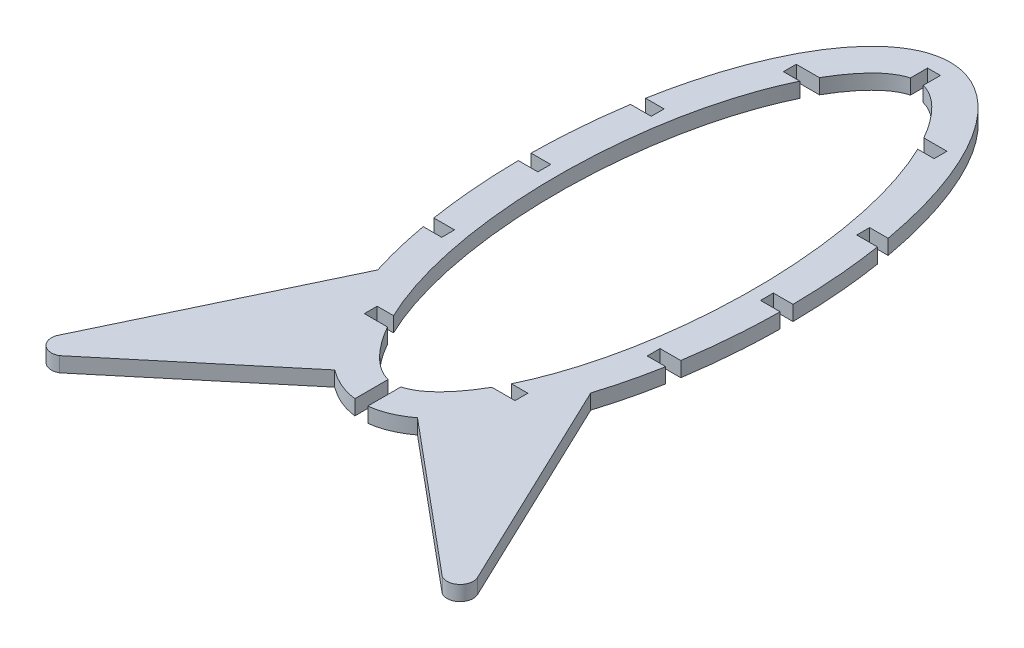
SolidWorks part; units mm, degrees
ref_plane "Front Plane" through (0, 0, 0) normal (0, 0, 1) x (1, 0, 0)
ref_plane "Top Plane" through (0, 0, 0) normal (0, 1, 0) x (1, 0, 0)
ref_plane "Right Plane" through (0, 0, 0) normal (1, 0, 0) x (0, 0, -1)
sketch "Sketch1" plane through (0, 0, 0) normal (0, 1, 0) x (1, 0, 0)
  line L2 (25.4, 0) -> (-45.1447, 0) construction
  line L3 (21.59, 0) -> (30.3971, 0) construction
  line L4 (21.59, 1.2446) -> (25.394, 1.2446)
  line L5 (21.59, 1.2446) -> (21.59, -1.2446)
  line L6 (21.59, -1.2446) -> (25.394, -1.2446)
  line L8 (37.0979, -78.485) -> (8.0291, -54.2196)
  line L9 (40.6569, -75.1899) -> (20.6588, -33.2492)
  line L10 (23.7402, 20.32) -> (29.3413, 20.32) construction
  line L11 (19.9302, 21.5646) -> (23.5224, 21.5646)
  line L12 (19.9302, 21.5646) -> (19.9302, 19.0754)
  line L13 (19.9302, 19.0754) -> (23.9434, 19.0754)
  line L19 (14.0482, 40.64) -> (-23.5224, 40.64) construction
  line L20 (0, 57.15) -> (0, 53.975) construction
  line L21 (-37.0979, -78.485) -> (-8.0291, -54.2196)
  line L22 (-14.6132, -41.8846) -> (-10.1242, -41.8846)
  line L23 (-14.6132, -41.8846) -> (-14.6132, -39.3954)
  line L24 (-14.6132, -39.3954) -> (-11.4313, -39.3954)
  line L25 (19.9302, -21.5646) -> (23.5224, -21.5646)
  line L26 (19.9302, -21.5646) -> (19.9302, -19.0754)
  line L27 (19.9302, -19.0754) -> (23.9434, -19.0754)
  line L28 (-40.6569, -75.1899) -> (-20.6588, -33.2492)
  line L29 (14.6132, 41.8846) -> (10.1242, 41.8846)
  line L30 (14.6132, 41.8846) -> (14.6132, 39.3954)
  line L31 (14.6132, 39.3954) -> (11.4313, 39.3954)
  line L32 (-19.9302, -21.5646) -> (-23.5224, -21.5646)
  line L33 (-19.9302, -21.5646) -> (-19.9302, -19.0754)
  line L34 (-19.9302, -19.0754) -> (-23.9434, -19.0754)
  line L35 (-21.59, 1.2446) -> (-21.59, -1.2446)
  line L36 (-21.59, 1.2446) -> (-25.394, 1.2446)
  line L37 (-21.59, -1.2446) -> (-25.394, -1.2446)
  line L38 (-19.9302, 21.5646) -> (-23.5224, 21.5646)
  line L39 (-19.9302, 21.5646) -> (-19.9302, 19.0754)
  line L40 (-19.9302, 19.0754) -> (-23.9434, 19.0754)
  line L41 (14.6132, -39.3954) -> (11.4313, -39.3954)
  line L42 (-14.6132, 41.8846) -> (-10.1242, 41.8846)
  line L43 (-14.6132, 41.8846) -> (-14.6132, 39.3954)
  line L44 (-14.6132, 39.3954) -> (-11.4313, 39.3954)
  line L46 (0, 39.3954) -> (0, -57.15) construction
  line L47 (14.6132, -41.8846) -> (14.6132, -39.3954)
  line L48 (14.6132, -41.8846) -> (10.1242, -41.8846)
  line L49 (1.2446, -53.975) -> (1.2446, -50.6449)
  line L50 (-1.2446, 53.975) -> (1.2446, 53.975)
  line L51 (-1.2446, 53.975) -> (-1.2446, 50.6449)
  line L53 (1.2446, 53.975) -> (1.2446, 50.6449)
  line L54 (1.2446, -53.975) -> (1.2446, -57.0814)
  line L55 (-1.2446, -53.975) -> (-1.2446, -50.6449)
  line L56 (-1.2446, -53.975) -> (-1.2446, -57.0814)
  arc A0 (37.0979, -78.485) -> (40.6569, -75.1899) centre (38.3642, -76.2831) ccw
  arc A1 (-37.0979, -78.485) -> (-40.6569, -75.1899) centre (-38.3642, -76.2831) cw
  ellipse E0 centre (0, 0) end of major axis (0, 57.15) minor radius 25.4 (-23.9434, 19.0754) -> (-25.394, 1.2446) ccw
  ellipse E1 centre (0, 0) end of major axis (0, 57.15) minor radius 25.4 (-25.394, -1.2446) -> (-23.9434, -19.0754) ccw
  ellipse E2 centre (0, 0) end of major axis (0, 57.15) minor radius 25.4 (-23.5224, -21.5646) -> (-20.6588, -33.2492) ccw
  ellipse E3 centre (0, 0) end of major axis (0, 57.15) minor radius 25.4 (23.9434, -19.0754) -> (25.394, -1.2446) ccw
  ellipse E4 centre (0, 0) end of major axis (0, 57.15) minor radius 25.4 (25.394, 1.2446) -> (23.9434, 19.0754) ccw
  ellipse E5 centre (0, 0) end of major axis (0, 57.15) minor radius 25.4 (23.5224, 21.5646) -> (-23.5224, 21.5646) ccw
  ellipse E6 centre (0, 0) end of major axis (0, 57.15) minor radius 25.4 (1.2446, -57.0814) -> (8.0291, -54.2196) ccw
  ellipse E7 centre (0, 0) end of major axis (0, 57.15) minor radius 25.4 (-8.0291, -54.2196) -> (-1.2446, -57.0814) ccw
  ellipse E8 centre (0, 0) end of major axis (0, 57.15) minor radius 25.4 (20.6588, -33.2492) -> (23.5224, -21.5646) ccw
  spline S0 degree 3 poles (10.1242, 41.8846) (9.6963, 42.6376) (8.1175, 45.2063) (5.3181, 48.5143) (2.7975, 50.1532) (1.5926, 50.559) (1.2446, 50.6449) knots -0.663564 -0.663564 -0.663564 -0.663564 -0.589049 -0.392699 -0.19635 -0.109038 -0.109038 -0.109038 -0.109038
  spline S1 degree 3 poles (1.2446, -50.6449) (1.5926, -50.559) (2.7975, -50.1532) (5.3181, -48.5143) (8.1175, -45.2063) (9.6963, -42.6376) (10.1242, -41.8846) knots -3.032554 -3.032554 -3.032554 -3.032554 -2.945243 -2.748894 -2.552544 -2.478028 -2.478028 -2.478028 -2.478028
  spline S2 degree 3 poles (-1.2446, -50.6449) (-1.5926, -50.559) (-2.7975, -50.1532) (-5.3181, -48.5143) (-8.1175, -45.2063) (-9.6963, -42.6376) (-10.1242, -41.8846) knots -3.032554 -3.032554 -3.032554 -3.032554 -2.945243 -2.748894 -2.552544 -2.478028 -2.478028 -2.478028 -2.478028
  spline S3 degree 3 poles (-10.1242, 41.8846) (-9.6963, 42.6376) (-8.1175, 45.2063) (-5.3181, 48.5143) (-2.7975, 50.1532) (-1.5926, 50.559) (-1.2446, 50.6449) knots -0.663564 -0.663564 -0.663564 -0.663564 -0.589049 -0.392699 -0.19635 -0.109038 -0.109038 -0.109038 -0.109038
  spline S4 degree 3 poles (-11.4313, -39.3954) (-11.6771, -38.8896) (-12.9878, -36.0709) (-15.1482, -30.1662) (-18.0998, -17.7755) (-19.6835, 0) (-18.0998, 17.7755) (-15.1482, 30.1662) (-12.9878, 36.0709) (-11.6771, 38.8896) (-11.4313, 39.3954) knots -2.400746 -2.400746 -2.400746 -2.400746 -2.356194 -2.159845 -1.963495 -1.570796 -1.178097 -0.981748 -0.785398 -0.740847 -0.740847 -0.740847 -0.740847
  spline S5 degree 3 poles (11.4313, -39.3954) (11.6771, -38.8896) (12.9878, -36.0709) (15.1482, -30.1662) (18.0998, -17.7755) (19.6835, 0) (18.0998, 17.7755) (15.1482, 30.1662) (12.9878, 36.0709) (11.6771, 38.8896) (11.4313, 39.3954) knots -2.400746 -2.400746 -2.400746 -2.400746 -2.356194 -2.159845 -1.963495 -1.570796 -1.178097 -0.981748 -0.785398 -0.740847 -0.740847 -0.740847 -0.740847
  point P25 (19.9302, 20.32)
  point P35 (44.1664, -82.55)
  dimension "D5" = 2.54
  dimension "D1" = 114.3
  dimension "D2" = 25.4
  dimension "D3" = 25.4
  dimension "D4" = 2.4892
  dimension "D6" = 3.81
  dimension "D7" = 2.4892
  dimension "D8" = 2.4892
  dimension "D9" = 3.81
  dimension "D10" = 2.4892
  dimension "D11" = 39.8605
  dimension "D12" = 29.2264
extrude "Boss-Extrude1" add sketch "Sketch1" along normal blind 2.8956
equation "\"thickness\"= 0.114"
